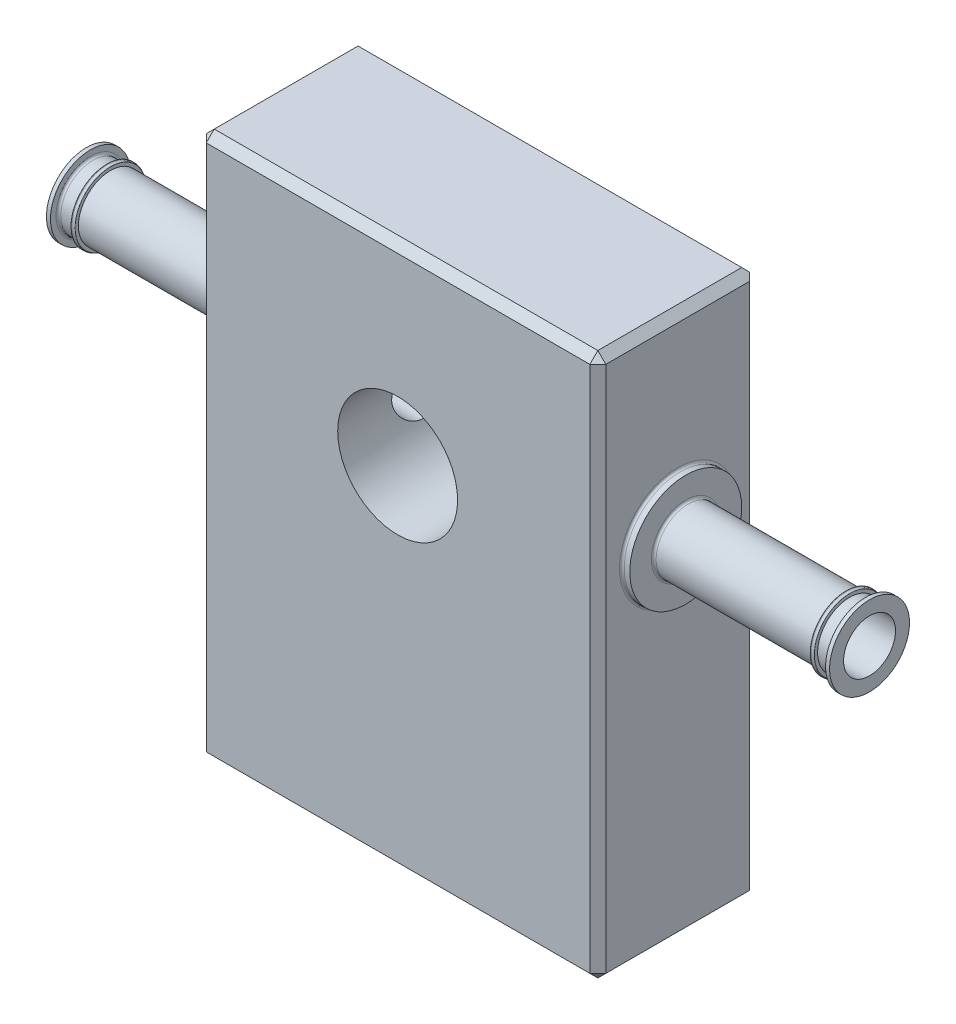
SolidWorks part; units mm, degrees
ref_plane "Piano frontale" through (0, 0, 0) normal (0, 0, 1) x (1, 0, 0)
ref_plane "Piano superiore" through (0, 0, 0) normal (0, 1, 0) x (1, 0, 0)
ref_plane "Piano destro" through (0, 0, 0) normal (1, 0, 0) x (0, 0, -1)
sketch "Schizzo1" plane through (0, 0, 0) normal (0, 0, 1) x (1, 0, 0)
  line L1 (-25, 50) -> (25, 50)
  line L2 (-25, 50) -> (-25, -18)
  line L3 (-25, -18) -> (25, -18)
  line L4 (25, 50) -> (25, -18)
  line L5 (-16.05, -18) -> (16.05, -18)
  line L6 (-16.05, -18) -> (-16.05, 42)
  line L7 (-16.05, 42) -> (16.05, 42)
  line L8 (16.05, -18) -> (16.05, 42)
  dimension "D1" = 50
  dimension "D2" = 68
  dimension "D3" = 25
  dimension "D4" = 50
  dimension "D5" = 32.1
  dimension "D6" = 16.05
  dimension "D7" = 60
extrude "Estrusione-Estrusione1" add sketch "Schizzo1" along normal blind 4 contours L8 L3 L4 L1 L2 L6 L7 region at (0, 49.156, 0)
sketch "Schizzo2" plane through (0, 0, 4) normal (0, 0, 1) x (1, 0, 0)
  line L1 (-25, 50) -> (25, 50)
  line L2 (-25, 50) -> (-25, -18)
  line L3 (-25, -18) -> (25, -18)
  line L4 (25, 50) -> (25, -18)
extrude "Estrusione-Estrusione2" add sketch "Schizzo2" along normal blind 16
sketch "Schizzo3" plane through (0, 0, 4) normal (0, 0, -1) x (-1, 0, 0)
  line L0 (16.05, 42) -> (-16.05, 42) construction
  line L3 (16.05, -18) -> (16.05, 42) construction
  circle A0 centre (0.05, 26) radius 7.5
  point P4 (0, 0)
  point P6 (16, 24.5505)
  dimension "D1" = 15
  dimension "D2" = 16
  dimension "D3" = 16
extrude "Taglio-Estrusione1" cut sketch "Schizzo3" against normal blind 16
sketch "Schizzo4" plane through (25, 0, 0) normal (1, 0, 0) x (0, 0, -1)
  line L1 (0, 50) -> (0, -18) construction
  line L2 (-20, 50) -> (0, 50) construction
  circle A0 centre (-10, 26) radius 7
  dimension "D2" = 14
  dimension "D3" = 24
  dimension "D1" = 10
extrude "Estrusione-Estrusione3" add sketch "Schizzo4" along normal blind 1
sketch "Schizzo5" plane through (26, 0, 0) normal (1, 0, 0) x (0, 0, -1)
  circle A0 centre (-10, 26) radius 4
  dimension "D1" = 8
extrude "Estrusione-Estrusione4" add sketch "Schizzo5" along normal blind 20
sketch "Schizzo6" plane through (46, 0, 0) normal (1, 0, 0) x (0, 0, -1)
  circle A0 centre (-10, 26) radius 4.5
  dimension "D1" = 9
extrude "Estrusione-Estrusione5" add sketch "Schizzo6" along normal blind 0.5
sketch "Schizzo7" plane through (46.5, 0, 0) normal (1, 0, 0) x (0, 0, -1)
  circle A0 centre (-10, 26) radius 4 construction
  circle A1 centre (-10, 26) radius 4
extrude "Estrusione-Estrusione6" add sketch "Schizzo7" along normal blind 2
sketch "Schizzo8" plane through (48.5, 0, 0) normal (1, 0, 0) x (0, 0, -1)
  circle A0 centre (-10, 26) radius 5
  dimension "D1" = 10
extrude "Estrusione-Estrusione7" add sketch "Schizzo8" along normal blind 0.5
fillet "Raccordo1" radius 0.3 1 edges at (25, 26, 3)
fillet "Raccordo2" radius 0.3 1 edges at (26, 26, 6)
fillet "Raccordo3" radius 0.3 1 edges at (48.5, 26, 6)
fillet "Raccordo6" radius 0.3 1 edges at (46, 26, 5.5) second distance 0.1 first distance on face at (46, 26, 6)
fillet "Raccordo7" radius 0.3 1 edges at (46.5, 26, 5.5) second distance 0.1
sketch "Schizzo9" plane through (49, 0, 0) normal (1, 0, 0) x (0, 0, -1)
  circle A0 centre (-10, 26) radius 3.25
  dimension "D1" = 6.5
extrude "Taglio-Estrusione3" cut sketch "Schizzo9" against normal up to next contours A0
mirror "Specchia4" about plane through (0, 0, 0) normal (1, 0, 0) of "Estrusione-Estrusione7", "Estrusione-Estrusione6", "Estrusione-Estrusione5", "Estrusione-Estrusione4", "Estrusione-Estrusione3"
fillet "Raccordo8" radius 0.3 1 edges at (-46, 26, 5.5) second distance 0.1 first distance on face at (-46.5, 26, 5.5)
fillet "Raccordo9" radius 0.3 1 edges at (-46.5, 26, 5.5) second distance 0.1 first distance on face at (-46.5, 26, 6)
fillet "Raccordo12" radius 0.3 2 edges at (-26, 26, 6) (-25, 26, 3)
fillet "Raccordo13" radius 0.3 1 edges at (-48.5, 26, 6)
mirror "Specchia9" about plane through (0, 0, 0) normal (1, 0, 0) of "Taglio-Estrusione3"
chamfer "Smusso1" distance 1 angle 45 5 edges at (-20.525, -18, 0) (20.525, -18, 0) (-25, 16, 0) (0, 50, 0) (25, 16, 0)
chamfer "Smusso2" distance 1 angle 45 8 edges at (-25, 16, 20) (-25, 50, 10.5) (0, 50, 20) (25, 50, 10.5) (25, 16, 20) (25, -18, 10.5) (0, -18, 20) (-25, -18, 10.5)
sketch "Schizzo10" plane through (0, 0, 0) normal (0, 0, -1) x (-1, 0, 0)
  circle A0 centre (0.05, 26) radius 28
  point P3 (0, 0)
  dimension "D1" = 56
hole_wizard "Foro per Vite M1-1" positions "Schizzo27" profile "Schizzo26" hole size "M1" standard "ISO"
sketch "Schizzo27" plane through (0, 0, 0) normal (0, 0, -1) x (-1, 0, 0)
  circle A0 centre (0.05, 26) radius 28 construction
  point P0 (-19.748, 45.8)
  dimension "D1" = 19.8
sketch "Schizzo26" plane through (19.748, 45.8, 0) normal (1, 0, 0) x (0, 1, 0)
  line L0 (0, 0) -> (0, 15)
  line L1 (0, 15) -> (2.5, 15)
  line L2 (2.5, 15) -> (2.5, 0)
  line L5 (2.5, 0) -> (0, 0)
  line L10 (0, 15) -> (-2.5, 15) construction
  line L11 (0, -6.35) -> (0, 107.95) construction
  dimension "Hole Dia." = 5
  dimension "Hole Depth" = 15
  dimension "Drill Angle" = 180
pattern_circular "RipetizioneCircolare4" count 4 over 360 about axis through (-0.05, 26, 4) along (0, 0, -1) of "Foro per Vite M1-1"
